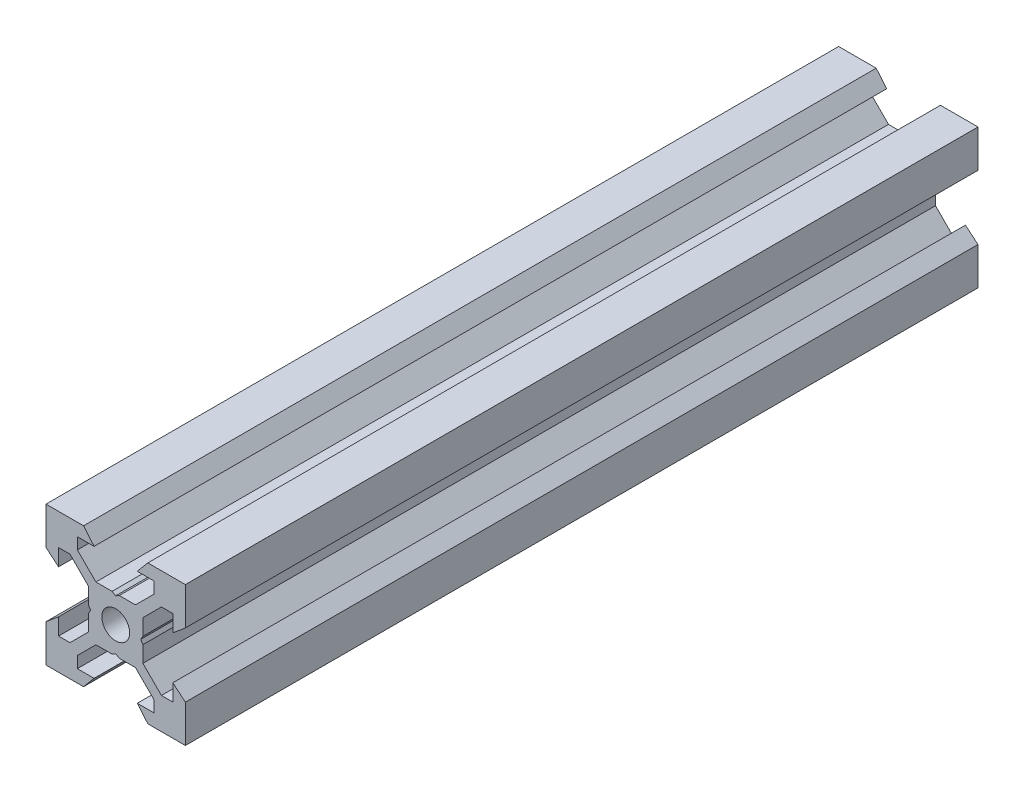
SolidWorks part; units mm, degrees
ref_plane "Front Plane" through (0, 0, 0) normal (0, 0, 1) x (1, 0, 0)
ref_plane "Top Plane" through (0, 0, 0) normal (0, 1, 0) x (1, 0, 0)
ref_plane "Right Plane" through (0, 0, 0) normal (1, 0, 0) x (0, 0, -1)
sketch "Sketch1" plane through (0, 0, 0) normal (0, 0, 1) x (1, 0, 0)
  line L0 (10, 10) -> (4.6104, 10) construction
  line L1 (10, 10) -> (10, 4.6104) construction
  line L2 (10, -10) -> (10, -4.6104) construction
  line L3 (10, -10) -> (4.6104, -10) construction
  line L4 (10, 10) -> (10, 4.6104)
  line L5 (6.5607, 5.5) -> (8.2, 5.5)
  line L6 (5.5, 8.2) -> (5.5, 6.5607)
  line L7 (10, 10) -> (4.6104, 10)
  line L8 (10, 10) -> (10, 4.6104)
  line L9 (6.5607, 5.5) -> (3.9, 2.8393)
  line L10 (5.5, 6.5607) -> (2.8393, 3.9)
  line L11 (10, 4.6104) -> (8.2, 3.1)
  line L12 (4.6104, 10) -> (3.1, 8.2)
  line L13 (8.2, 3.1) -> (8.2, 5.5)
  line L14 (3.1, 8.2) -> (5.5, 8.2)
  line L15 (-6.5607, 5.5) -> (-8.2, 5.5)
  line L16 (6.5607, -5.5) -> (8.2, -5.5)
  line L17 (3.1, -8.2) -> (5.5, -8.2)
  line L18 (8.2, -3.1) -> (8.2, -5.5)
  line L19 (4.6104, -10) -> (3.1, -8.2)
  line L20 (10, -4.6104) -> (8.2, -3.1)
  line L21 (0.5196, -3.9) -> (0, -3.6)
  line L22 (0.5196, 3.9) -> (0, 3.6)
  line L23 (3.6, 0) -> (3.9, -0.5196)
  line L24 (3.9, 0.5196) -> (3.6, 0)
  line L25 (3.9, 0.5196) -> (3.9, 2.8393)
  line L26 (2.8393, 3.9) -> (0.5196, 3.9)
  line L27 (3.9, -2.8393) -> (3.9, -0.5196)
  line L28 (2.8393, -3.9) -> (0.5196, -3.9)
  line L29 (5.5, -6.5607) -> (2.8393, -3.9)
  line L30 (6.5607, -5.5) -> (3.9, -2.8393)
  line L31 (10, -10) -> (10, -4.6104)
  line L32 (10, -10) -> (4.6104, -10)
  line L33 (5.5, -8.2) -> (5.5, -6.5607)
  line L34 (-6.5607, -5.5) -> (-8.2, -5.5)
  line L35 (10, -10) -> (10, -4.6104)
  line L36 (0, 0) -> (0, 8.2) construction
  line L37 (-10, -10) -> (-4.6104, -10) construction
  line L38 (-10, -10) -> (-10, -4.6104) construction
  line L39 (-10, 10) -> (-10, 4.6104) construction
  line L40 (-10, 10) -> (-4.6104, 10) construction
  line L41 (-10, -10) -> (-10, -4.6104)
  line L43 (-5.5, -8.2) -> (-5.5, -6.5607)
  line L44 (-10, -10) -> (-4.6104, -10)
  line L45 (-10, -10) -> (-10, -4.6104)
  line L46 (-6.5607, -5.5) -> (-3.9, -2.8393)
  line L47 (-5.5, -6.5607) -> (-2.8393, -3.9)
  line L48 (-2.8393, -3.9) -> (-0.5196, -3.9)
  line L49 (-3.9, -2.8393) -> (-3.9, -0.5196)
  line L50 (-2.8393, 3.9) -> (-0.5196, 3.9)
  line L51 (-3.9, 0.5196) -> (-3.9, 2.8393)
  line L52 (-3.9, 0.5196) -> (-3.6, 0)
  line L53 (-3.6, 0) -> (-3.9, -0.5196)
  line L54 (-0.5196, 3.9) -> (0, 3.6)
  line L55 (-0.5196, -3.9) -> (0, -3.6)
  line L56 (-10, -4.6104) -> (-8.2, -3.1)
  line L57 (-4.6104, -10) -> (-3.1, -8.2)
  line L58 (-8.2, -3.1) -> (-8.2, -5.5)
  line L59 (-3.1, -8.2) -> (-5.5, -8.2)
  line L60 (-10, -10) -> (10, -10) construction
  line L61 (-10, -10) -> (-10, 10) construction
  line L62 (-3.1, 8.2) -> (-5.5, 8.2)
  line L63 (-8.2, 3.1) -> (-8.2, 5.5)
  line L64 (-4.6104, 10) -> (-3.1, 8.2)
  line L65 (-10, 4.6104) -> (-8.2, 3.1)
  line L66 (-5.5, 6.5607) -> (-2.8393, 3.9)
  line L67 (-6.5607, 5.5) -> (-3.9, 2.8393)
  line L68 (-10, 10) -> (-10, 4.6104)
  line L69 (-10, 10) -> (-4.6104, 10)
  line L70 (-5.5, 8.2) -> (-5.5, 6.5607)
  line L71 (-10, 10) -> (10, 10) construction
  line L72 (-10, 10) -> (-10, 4.6104)
  line L73 (10, -10) -> (10, 10) construction
  line L74 (-10, -10) -> (10, 10) construction
  line L75 (-10, 10) -> (10, -10) construction
  circle A0 centre (0, 0) radius 2
  dimension "D7" = 4
  dimension "D1" = 20
  dimension "D2" = 5.3896
  dimension "D3" = 4.5
  dimension "D4" = 50
  dimension "D5" = 1.8
  dimension "D6" = 1.5104
  dimension "D8" = 5.5
  dimension "D9" = 120
  dimension "D10" = 0.3
  dimension "D11" = 2.3197
  dimension "D12" = 7.8
  dimension "D13" = 7.8
  dimension "D14" = 1.5
  dimension "D15" = 2.6607
extrude "Boss-Extrude1" add sketch "Sketch1" along normal mid plane 113.74 contours L70 L62 L64 L69 L68 L65 L63 L15 L67 L51 L52 L53 L49 L46 L34 L58 L56 L41 L44 L57 L59 L43 L47 L48 L55 L21 L28 L29 L33 L17 L19 L32 L31 L20 L18 L16 L30 L27 L23 L24 L25 L9 L5 L13 L11 L4 L7 L12 L14 L6 L10 region at (9.7172, 7.3052, 0)
